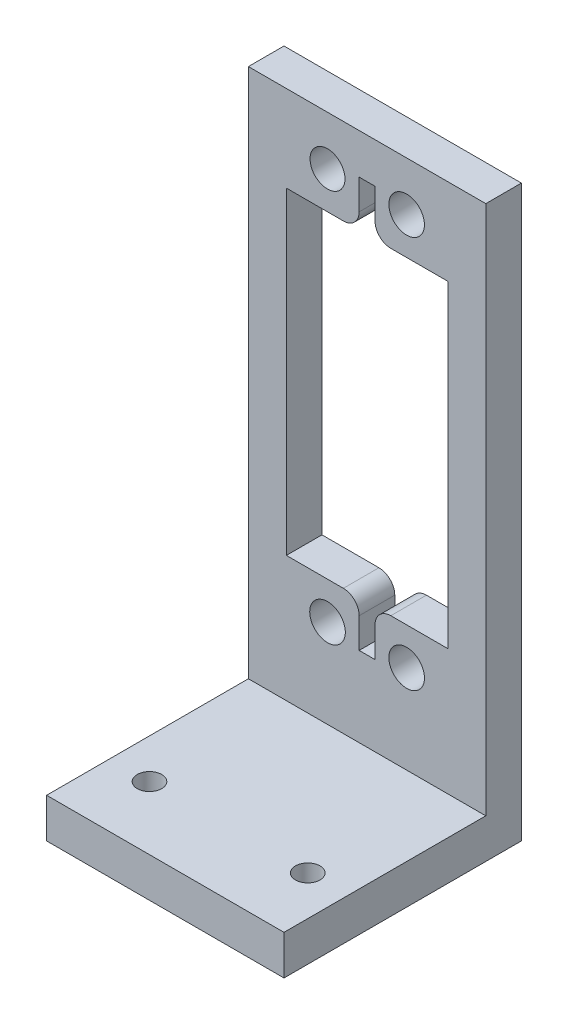
SolidWorks part; units mm, degrees
ref_plane "前视基准面" through (0, 0, 0) normal (0, 0, 1) x (1, 0, 0)
ref_plane "上视基准面" through (0, 0, 0) normal (0, 1, 0) x (1, 0, 0)
ref_plane "右视基准面" through (0, 0, 0) normal (1, 0, 0) x (0, 0, -1)
sketch "草图1" plane through (0, 0, 0) normal (0, 0, 1) x (1, 0, 0)
  line L1 (10.2, -20.1) -> (-10.2, -20.1)
  line L2 (10.2, -20.1) -> (10.2, 20.1)
  line L3 (10.2, 20.1) -> (-10.2, 20.1)
  line L4 (-10.2, -20.1) -> (-10.2, 20.1)
  line L5 (10.2, -20.1) -> (-10.2, 20.1) construction
  line L6 (10.2, 20.1) -> (-10.2, -20.1) construction
  line L7 (15, -31) -> (-15, -31)
  line L8 (15, -31) -> (15, 31)
  line L9 (15, 31) -> (-15, 31)
  line L10 (-15, -31) -> (-15, 31)
  line L11 (15, -31) -> (-15, 31) construction
  line L12 (15, 31) -> (-15, -31) construction
  point P0 (0, 0)
  point P5 (0, 0)
  dimension "D1" = 20.4
  dimension "D2" = 40.2
  dimension "D3" = 30
  dimension "D4" = 62
extrude "凸台-拉伸1" add sketch "草图1" along normal blind 4.5
sketch "草图3" plane through (0, 0, 0) normal (0, 0, -1) x (-1, 0, 0)
  circle A0 centre (-5, -24.8) radius 2.25
  circle A1 centre (5, -24.8) radius 2.25
  circle A2 centre (-5, 24.8) radius 2.25
  circle A3 centre (5, 24.8) radius 2.2065
extrude "切除-拉伸1" cut sketch "草图3" against normal through all
sketch "草图4" plane through (0, 31, 0) normal (0, 1, 0) x (1, 0, 0)
  line L4 (15, 0) -> (-15, 0)
  line L5 (-15, 0) -> (-15, -4.5)
  line L6 (-15, -4.5) -> (15, -4.5)
  line L7 (15, -4.5) -> (15, 0)
  line L8 (15, 0) -> (-15, 0)
  line L9 (-15, 0) -> (-15, -4.5)
  line L10 (-15, -4.5) -> (15, -4.5)
  line L11 (15, -4.5) -> (15, 0)
  dimension "D1" = 0
sketch "草图5" plane through (0, -31, 0) normal (0, -1, 0) x (1, 0, 0)
  line L4 (-15, 0) -> (15, 0)
  line L5 (15, 0) -> (15, 4.5)
  line L6 (15, 4.5) -> (-15, 4.5)
  line L7 (-15, 4.5) -> (-15, 0)
  line L8 (-15, 0) -> (15, 0)
  line L9 (15, 0) -> (15, 4.5)
  line L10 (15, 4.5) -> (-15, 4.5)
  line L11 (-15, 4.5) -> (-15, 0)
  dimension "D1" = 0
extrude "凸台-拉伸3" add sketch "草图5" along normal blind 5
sketch "草图6" plane through (0, -36, 0) normal (0, -1, 0) x (1, 0, 0)
  line L0 (-15, 4.5) -> (-15, 0) construction
  line L1 (15, 0) -> (-15, 0)
  line L2 (15, 0) -> (15, 30)
  line L3 (15, 30) -> (-15, 30)
  line L4 (-15, 0) -> (-15, 30)
  dimension "D1" = 30
extrude "凸台-拉伸4" add sketch "草图6" along normal blind 5
sketch "草图7" plane through (0, -41, 0) normal (0, -1, 0) x (1, 0, 0)
  line L0 (0, 30) -> (0, 22) construction
  line L1 (15, 30) -> (-15, 30) construction
  line L2 (0, 22) -> (10, 22) construction
  circle A0 centre (10, 22) radius 1.55
  circle A1 centre (-10, 22) radius 1.55
  dimension "D1" = 8
  dimension "D3" = 3.1
  dimension "D2" = 10
extrude "切除-拉伸2" cut sketch "草图7" against normal through all
sketch "草图8" plane through (0, 0, 4.5) normal (0, 0, 1) x (1, 0, 0)
  line L0 (0, -20.1) -> (0, -26.5553) construction
  line L1 (-10.2, -20.1) -> (10.2, -20.1) construction
  line L2 (0, 0) -> (13.0244, 0) construction
  line L3 (1, 20.1) -> (-1, 25.9) construction
  line L4 (1, -25.9) -> (-1, -25.9)
  line L5 (1, -25.9) -> (1, -20.1)
  line L6 (1, -20.1) -> (-1, -20.1)
  line L7 (-1, -25.9) -> (-1, -20.1)
  line L8 (1, -25.9) -> (-1, -20.1) construction
  line L9 (1, -20.1) -> (-1, -25.9) construction
  line L10 (1, 25.9) -> (-1, 20.1) construction
  line L11 (0, 20.1) -> (0, 26.5553) construction
  line L12 (-1, 25.9) -> (-1, 20.1)
  line L13 (1, 20.1) -> (-1, 20.1)
  line L14 (1, 25.9) -> (1, 20.1)
  line L15 (1, 25.9) -> (-1, 25.9)
  point P7 (0, -23)
  point P18 (0, 23)
  dimension "D1" = 2
  dimension "D2" = 5.8
extrude "切除-拉伸3" cut sketch "草图8" against normal through all
fillet "圆角1" radius 2 4 edges at (1, 20.1, 2.25) (-1, 20.1, 2.25) (1, -20.1, 2.25) (-1, -20.1, 2.25)
